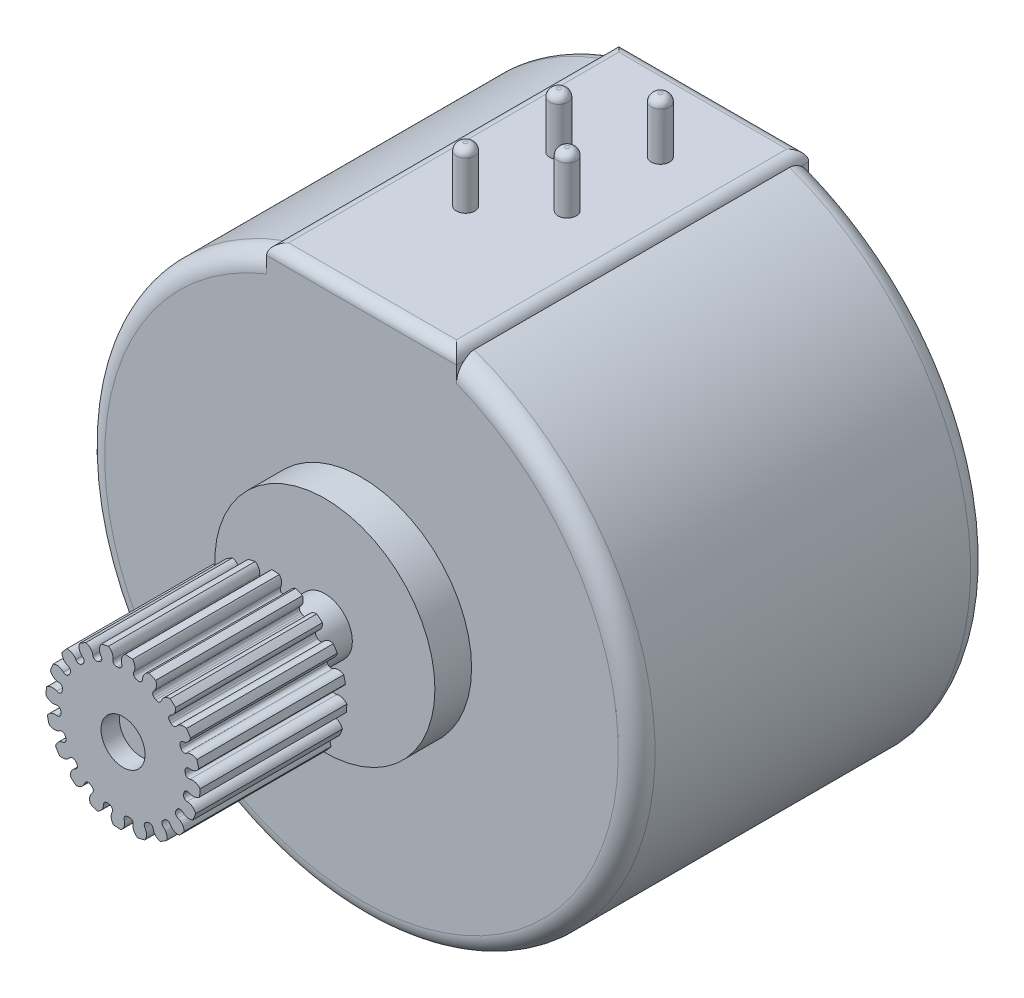
SolidWorks part; units mm, degrees
ref_plane "Ön Düzlem" through (0, 0, 0) normal (0, 0, 1) x (1, 0, 0)
ref_plane "Üst Düzlem" through (0, 0, 0) normal (0, 1, 0) x (1, 0, 0)
ref_plane "Sağ Düzlem" through (0, 0, 0) normal (1, 0, 0) x (0, 0, -1)
sketch "Çizim1" plane through (0, 0, 0) normal (0, 0, 1) x (1, 0, 0)
  line L1 (-2.5886, 7.0391) -> (-2.5886, 7.2391)
  line L2 (2.5886, 7.0391) -> (2.5886, 7.2391)
  line L3 (2.5886, 7.2391) -> (-2.5886, 7.2391)
  arc A0 (-2.5886, 7.0391) -> (2.5886, 7.0391) centre (0, 0) ccw
  dimension "D1" = 0.2
extrude "Yükseklik-Ekstrüzyon1" add sketch "Çizim1" along normal blind 9.6
fillet "Radyus1" radius 0.5 1 edges at (0, -7.5, 0) type face fillet first side face at (0, 3.5043, 0) second side face at (0, -0.2304, 4.8)
fillet "Radyus2" radius 0.5 1 edges at (0, -7.5, 9.6) type face fillet first side face at (0, 3.5043, 9.6) second side face at (0, -0.2304, 5.05)
sketch "Çizim2" plane through (0, 0, 9.6) normal (0, 0, 1) x (1, 0, 0)
  circle A0 centre (0, 0) radius 3
extrude "Yükseklik-Ekstrüzyon2" add sketch "Çizim2" along normal blind 1
sketch "Çizim3" plane through (0, 0, 10.6) normal (0, 0, 1) x (1, 0, 0)
  circle A0 centre (0, 0) radius 0.75
extrude "Yükseklik-Ekstrüzyon3" add sketch "Çizim3" along normal blind 1.5
sketch "Çizim4" plane through (0, 0, 12.1) normal (0, 0, 1) x (1, 0, 0)
  circle A0 centre (0, 0) radius 2.1
extrude "Yükseklik-Ekstrüzyon4" add sketch "Çizim4" along normal blind 4
sketch "Çizim5" plane through (0, 0, 16.1) normal (0, 0, 1) x (1, 0, 0)
  line L0 (-0.6896, 1.5538) -> (-1.4857, 3.3477) construction
  arc A0 (-0.5938, 2.0143) -> (-1.0144, 1.8388) centre (0, 0) ccw
  arc A1 (-0.6406, 1.5747) -> (-0.6823, 1.5571) centre (0, 0) ccw
  arc A2 (-0.5938, 2.0143) -> (-0.5962, 1.7246) centre (-0.3913, 1.8677) ccw
  arc A3 (-0.5962, 1.7246) -> (-0.6406, 1.5747) centre (-0.6782, 1.6673) cw
  arc A4 (-0.8213, 1.6332) -> (-1.0144, 1.8388) centre (-1.0683, 1.5947) ccw
  arc A5 (-0.6823, 1.5571) -> (-0.8213, 1.6332) centre (-0.7225, 1.6486) cw
  dimension "D1" = 0.4
  dimension "D2" = 4.2
  dimension "D3" = 0.5
  dimension "D4" = 0.4
  dimension "D5" = 0.1
  dimension "D6" = 0.1
extrude "Kes-Ekstrüzyon1" cut sketch "Çizim5" against normal blind 4
pattern_circular "Dairesel Çoğaltma1" count 20 over 360 about axis through (0, 0, 16.1) along (0, 0, 1) of "Kes-Ekstrüzyon1"
sketch "Çizim6" plane through (0, 0, 16.1) normal (0, 0, 1) x (1, 0, 0)
  circle A0 centre (0, 0) radius 0.6
extrude "Kes-Ekstrüzyon2" cut sketch "Çizim6" against normal blind 0.5
sketch "Çizim7" plane through (0, 0, 0) normal (0, 0, -1) x (-1, 0, 0)
  circle A0 centre (0, 0) radius 3
extrude "Yükseklik-Ekstrüzyon5" add sketch "Çizim7" along normal blind 0.8
sketch "Çizim8" plane through (0, 0, -0.8) normal (0, 0, -1) x (-1, 0, 0)
  circle A0 centre (0, 0) radius 0.75
extrude "Yükseklik-Ekstrüzyon6" add sketch "Çizim8" along normal blind 0.5
fillet "Radyus4" radius 0.3 1 edges at (-3, 0, -0.8) type face fillet first side face at (-3, 0, -0.8) second side face at (-3, 0, -0.8)
fillet "Radyus5" radius 0.3 1 edges at (-0.75, 0, -1.3)
fillet "Radyus6" radius 0.3 4 edges at (2.5886, 7.2391, 4.8) (0, 7.2391, 9.6) (-2.5886, 7.2391, 4.8) (0, 7.2391, 0)
sketch "Çizim9" plane through (0, 7.2391, 0) normal (0, 1, 0) x (1, 0, 0)
  line L0 (2.2886, -0.3) -> (-2.2886, -0.3) construction
  circle A0 centre (-0.7477, -6.0146) radius 0.25
  circle A1 centre (-0.7477, -3.4746) radius 0.25
  circle A2 centre (0.75, -4.7446) radius 0.25
  circle A3 centre (0.75, -2.2046) radius 0.25
  point P8 (0, -0.3)
  dimension "D5" = 0.5
  dimension "D6" = 0.5
  dimension "D7" = 0.5
  dimension "D8" = 0.5
  dimension "D1" = 2.54
  dimension "D2" = 2.54
  dimension "D3" = 1.27
  dimension "D4" = 0.75
extrude "Yükseklik-Ekstrüzyon7" add sketch "Çizim9" along normal blind 1.5
fillet "Radyus7" radius 0.2 1 edges at (-0.9977, 8.7391, 3.4746)
fillet "Radyus8" radius 0.2 1 edges at (-0.9977, 8.7391, 6.0146)
fillet "Radyus9" radius 0.2 1 edges at (0.5, 8.7391, 4.7446)
fillet "Radyus10" radius 0.2 1 edges at (0.5, 8.7391, 2.2046)
